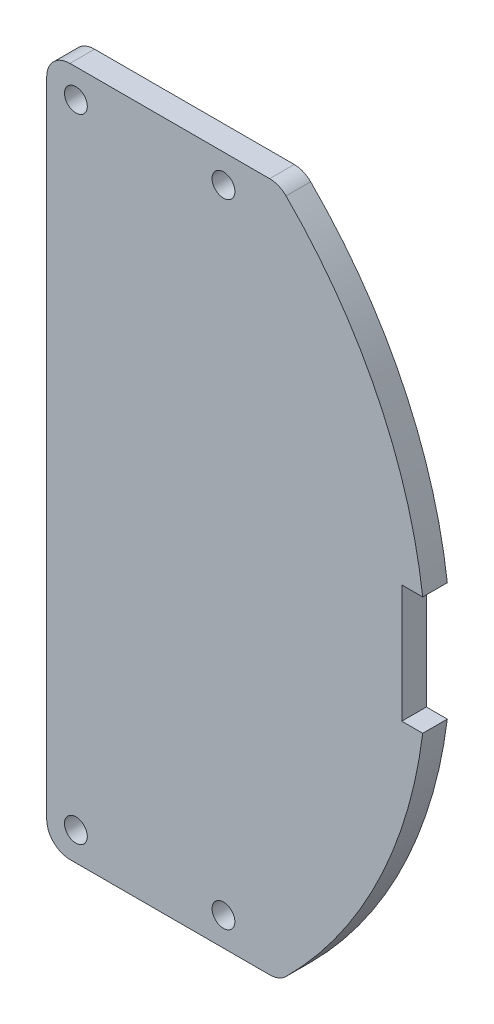
SolidWorks part; units mm, degrees
material "Delrin 2700 NC010, Low Viscosity Acetal Copolymer (SS)"
ref_plane "Front Plane" through (0, 0, 0) normal (0, 0, 1) x (1, 0, 0)
ref_plane "Top Plane" through (0, 0, 0) normal (0, 1, 0) x (1, 0, 0)
ref_plane "Right Plane" through (0, 0, 0) normal (1, 0, 0) x (0, 0, -1)
sketch "Sketch1" plane through (0, 0, 0) normal (0, 0, 1) x (1, 0, 0)
  line L2 (12.5875, 44.5) -> (42.5875, 44.5)
  line L5 (12.5875, -44.5) -> (12.5875, 44.5)
  line L8 (12.5875, -44.5) -> (42.5875, -44.5)
  arc A4 (42.5875, 44.5) -> (42.5875, -44.5) centre (0, 0) cw
  dimension "D2" = 30
extrude "Boss-Extrude1" add sketch "Sketch1" along normal blind 3.175
sketch "Sketch2" plane through (0, 0, 3.175) normal (0, 0, 1) x (1, 0, 0)
  line L0 (12.5875, 0) -> (61.595, 0) construction
  line L1 (12.5875, 44.5) -> (12.5875, -44.5) construction
  circle A0 centre (16.3543, -40.8119) radius 1.4732
  arc A1 (42.5875, -44.5) -> (42.5875, 44.5) centre (0, 0) ccw construction
  circle A2 centre (35.4043, -40.8119) radius 1.4732
  circle A3 centre (16.3543, 40.8119) radius 1.4732
  circle A4 centre (35.4043, 40.8119) radius 1.4732
  dimension "D1" = 2
extrude "Cut-Extrude1" cut sketch "Sketch2" against normal through all
sketch "Sketch3" plane through (0, 0, 3.175) normal (0, 0, 1) x (1, 0, 0)
  line L0 (58.42, 7.62) -> (61.1218, 7.62) construction
  line L1 (58.42, -7.62) -> (61.1218, -7.62) construction
  line L2 (58.42, 7.62) -> (58.42, -7.62) construction
  line L3 (58.42, 7.62) -> (61.1218, 7.62)
  line L4 (58.42, -7.62) -> (61.1218, -7.62)
  line L5 (58.42, 7.62) -> (58.42, -7.62)
  arc A0 (42.5875, -44.5) -> (42.5875, 44.5) centre (0, 0) ccw construction
  arc A1 (61.1218, -7.62) -> (61.1218, 7.62) centre (0, 0) ccw
extrude "Cut-Extrude2" cut sketch "Sketch3" against normal through all
fillet "Fillet1" radius 3 4 edges at (12.5875, -44.5, 1.5875) (42.5875, -44.5, 1.5875) (12.5875, 44.5, 1.5875) (42.5875, 44.5, 1.5875)
sketch "Sketch4" plane through (0, 0, 3.175) normal (0, 0, 1) x (1, 0, 0)
  line L0 (46.9295, -14.42) -> (8.8343, -14.42)
  line L1 (8.8343, -14.42) -> (8.8343, -24.58)
  line L2 (8.8343, -24.58) -> (46.9295, -24.58)
  arc A0 (46.9295, -24.58) -> (46.9295, -14.42) centre (46.9295, -19.5) ccw
extrude "Cut-Extrude3" [suppressed] cut sketch "Sketch4" against normal through all
fillet "Fillet2" [suppressed] radius 3
